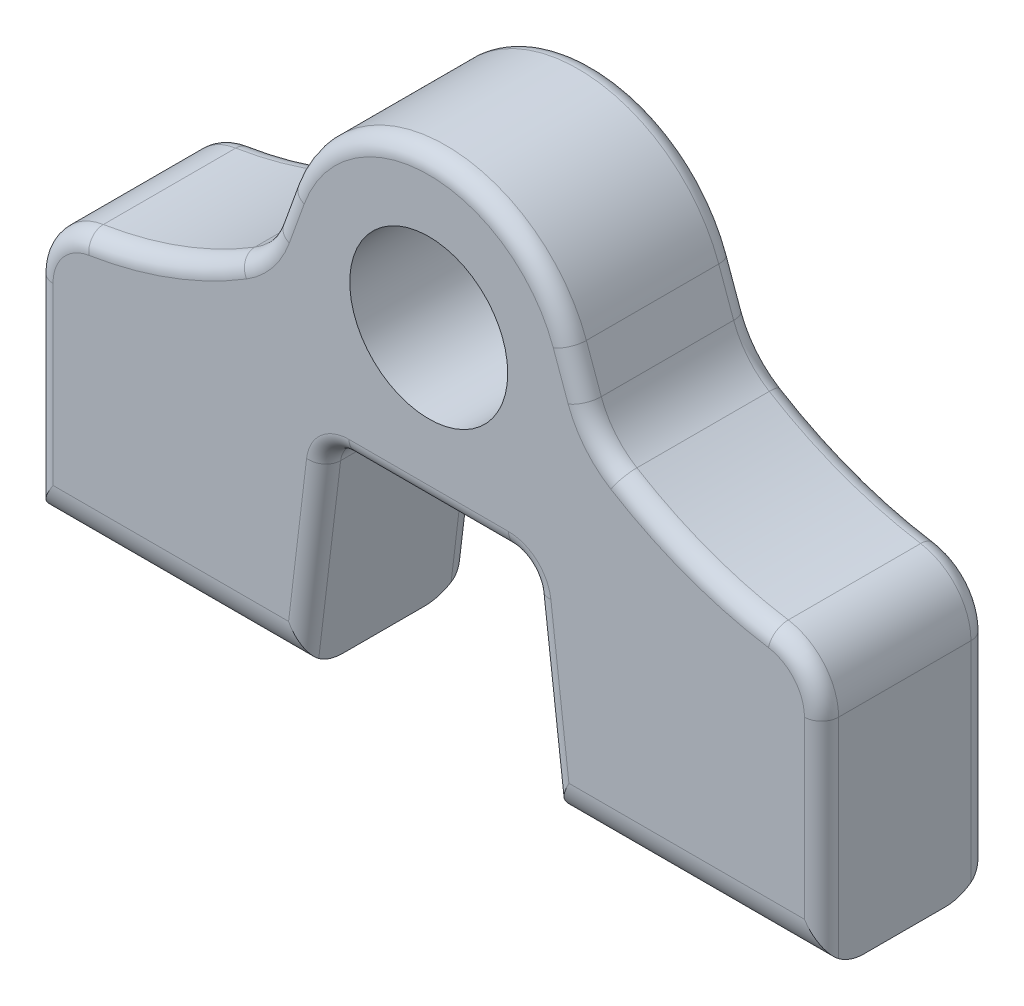
SolidWorks part; units mm, degrees
material "AISI 1020"
ref_plane "Alzado" through (0, 0, 0) normal (0, 0, 1) x (1, 0, 0)
ref_plane "Planta" through (0, 0, 0) normal (0, 1, 0) x (1, 0, 0)
ref_plane "Vista lateral" through (0, 0, 0) normal (1, 0, 0) x (0, 0, -1)
sketch "Croquis1" plane through (0, 0, 0) normal (0, 0, 1) x (1, 0, 0)
  line L0 (0, 17.5) -> (0, -21.4129) construction
  line L1 (16.4617, 5.9382) -> (18.2055, 1.1041)
  line L2 (-16.4617, 5.9382) -> (-18.2055, 1.1041)
  line L4 (15, -43) -> (46, -43)
  line L5 (46, -43) -> (46, -18.5096)
  line L6 (-15, -43) -> (-46, -43)
  line L7 (-46, -43) -> (-46, -18.5096)
  line L10 (46, -18.5096) -> (46, -17.5013)
  line L11 (-46, -18.5096) -> (-46, -17.5013)
  line L12 (-15, -43) -> (-12, -18)
  line L13 (-12, -18) -> (12, -18)
  line L14 (12, -18) -> (15, -43)
  arc A2 (16.4617, 5.9382) -> (-16.4617, 5.9382) centre (0, 0) ccw
  arc A3 (45.7743, -17.6757) -> (46, -18.5096) centre (40, -19.6861) cw construction
  arc A6 (-45.7743, -17.6757) -> (-46, -18.5096) centre (-40, -19.6861) ccw construction
  circle A7 centre (0, 0) radius 9.25
  arc A10 (40.1055, -10.5892) -> (22.3784, -4.0237) centre (47.7664, 37.3102) cw
  arc A11 (-40.1055, -10.5892) -> (-22.3784, -4.0237) centre (-47.7664, 37.3102) ccw
  arc A12 (-18.2055, 1.1041) -> (-22.3784, -4.0237) centre (-27.6122, 4.4974) cw
  arc A13 (18.2055, 1.1041) -> (22.3784, -4.0237) centre (27.6122, 4.4974) ccw
  arc A14 (-40.1055, -10.5892) -> (-46, -17.5013) centre (-39, -17.5013) ccw
  arc A15 (46, -17.5013) -> (40.1055, -10.5892) centre (39, -17.5013) ccw
  dimension "D1" = 40
  dimension "D2" = 17.5
  dimension "D3" = 18.5
  dimension "D4" = 10
  dimension "D5" = 7
  dimension "D7" = 43
  dimension "D8" = 30
  dimension "D9" = 18
  dimension "D6" = 92
  dimension "D10" = 3
  dimension "D11" = 3
extrude "Saliente-Extruir1" add sketch "Croquis1" along normal mid plane 19.5
fillet "Redondeo4" radius 3 2 edges at (12, -18, 0) (-12, -18, 0)
fillet "Redondeo5" radius 2 32 edges at (46, -30.2507, 9.75) (44.3263, -12.9592, 9.75) (30.919, -8.1783, 9.75) (19.8559, -1.8146, 9.75) (17.3336, 3.5211, 9.75) (0, 17.5, 9.75) (-17.3336, 3.5211, 9.75) (-19.8559, -1.8146, 9.75) (-30.919, -8.1783, 9.75) (-44.3263, -12.9592, 9.75) (-46, -30.2507, 9.75) (46, -30.2507, -9.75) (44.3263, -12.9592, -9.75) (30.919, -8.1783, -9.75) (19.8559, -1.8146, -9.75) (17.3336, 3.5211, -9.75) (0, 17.5, -9.75) (-17.3336, 3.5211, -9.75) (-19.8559, -1.8146, -9.75) (-30.919, -8.1783, -9.75) (-44.3263, -12.9592, -9.75) (-46, -30.2507, -9.75) (-13.6586, -31.8213, -9.75) (-11.3294, -18.7559, -9.75) (0, -18, -9.75) (11.3294, -18.7559, -9.75) (13.6586, -31.8213, 9.75) (11.3294, -18.7559, 9.75) (0, -18, 9.75) (-11.3294, -18.7559, 9.75) (13.6586, -31.8213, -9.75) (-13.6586, -31.8213, 9.75)
fillet "Redondeo6" radius 5 4 edges at (30.5072, -43, 9.75) (-30.5072, -43, 9.75) (30.5072, -43, -9.75) (-30.5072, -43, -9.75)
